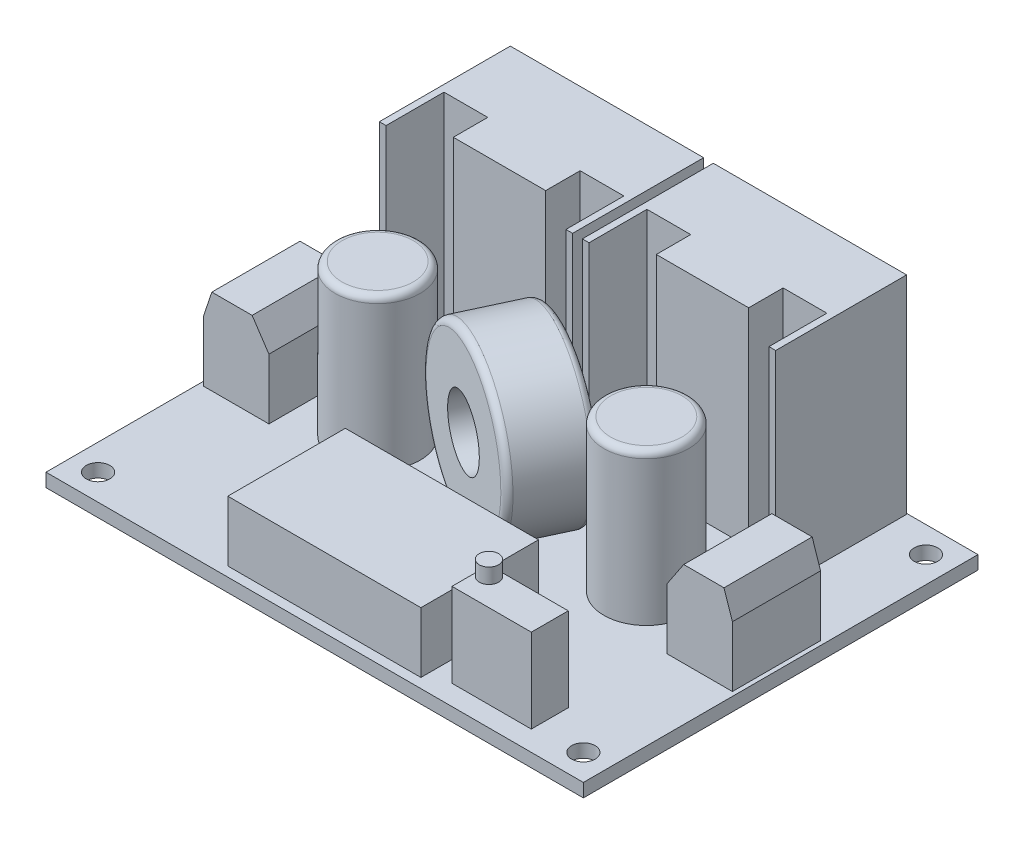
SolidWorks part; units mm, degrees
ref_plane "Front" through (0, 0, 0) normal (0, 0, 1) x (1, 0, 0)
ref_plane "Top" through (0, 0, 0) normal (0, 1, 0) x (1, 0, 0)
ref_plane "Right" through (0, 0, 0) normal (1, 0, 0) x (0, 0, -1)
sketch "Sketch1" plane through (0, 0, 0) normal (0, 1, 0) x (1, 0, 0)
  line L1 (-32, -23.5) -> (32, -23.5)
  line L2 (-32, -23.5) -> (-32, 23.5)
  line L3 (-32, 23.5) -> (32, 23.5)
  line L4 (32, -23.5) -> (32, 23.5)
  line L5 (-32, -23.5) -> (32, 23.5) construction
  line L6 (-32, 23.5) -> (32, -23.5) construction
  point P0 (0, 0)
  dimension "D1" = 47
  dimension "D2" = 64
extrude "Boss-Extrude1" add sketch "Sketch1" along normal blind 1.6
sketch "Sketch2" plane through (0, 1.6, 0) normal (0, 1, 0) x (1, 0, 0)
  line L0 (-27.6, 0) -> (27.6, 0) construction
  line L9 (-32, 23.5) -> (-32, -23.5) construction
  line L10 (-31.5, -5.25) -> (-23.7, -5.25)
  line L11 (-31.5, -5.25) -> (-31.5, 5.25)
  line L12 (-31.5, 5.25) -> (-23.7, 5.25)
  line L13 (-23.7, -5.25) -> (-23.7, 5.25)
  line L14 (-31.5, -5.25) -> (-23.7, 5.25) construction
  line L15 (-31.5, 5.25) -> (-23.7, -5.25) construction
  line L16 (23.7, -5.25) -> (31.5, -5.25)
  line L17 (23.7, -5.25) -> (23.7, 5.25)
  line L18 (23.7, 5.25) -> (31.5, 5.25)
  line L19 (31.5, -5.25) -> (31.5, 5.25)
  line L20 (23.7, -5.25) -> (31.5, 5.25) construction
  line L21 (23.7, 5.25) -> (31.5, -5.25) construction
  point P3 (0, 0)
  dimension "D1" = 7.8
  dimension "D2" = 10.5
  dimension "D3" = 0.5
extrude "Boss-Extrude2" add sketch "Sketch2" along normal blind 10.2
chamfer "Chamfer1" distance 3 distance2 2 2 edges at (23.7, 11.8, 0) (-23.7, 11.8, 0) first distance on face at (23.7, 6.7, 0) first distance on face at (-23.7, 6.7, 0)
chamfer "Chamfer2" distance 3 distance2 1 2 edges at (-31.5, 11.8, 0) (31.5, 11.8, 0) first distance on face at (-31.5, 6.7, 0) first distance on face at (31.5, 6.7, 0)
sketch "Sketch3" plane through (0, 1.6, 0) normal (0, 1, 0) x (1, 0, 0)
  line L0 (-16, 0) -> (16, 0) construction
  circle A0 centre (-16, 0) radius 5.05
  circle A1 centre (16, 0) radius 5.05
  point P8 (0, 0)
  dimension "D2" = 10.1
  dimension "D1" = 32
extrude "Boss-Extrude3" add sketch "Sketch3" along normal blind 18
ref_axis "Axis1" through (0, 0, 0) along (0, 1, 0)
ref_plane "Plane1" through (0, 0, 0) normal (-0.4226, 0, 0.9063) x (0, 1, 0)
sketch "Sketch4" plane through (0, 0, 0) normal (-0.4226, 0, 0.9063) x (0, 1, 0)
  circle A0 centre (11, 0) radius 10
  circle A1 centre (11, 0) radius 3.9
  dimension "D1" = 20
  dimension "D2" = 7.8
  dimension "D3" = 11
extrude "Boss-Extrude4" add sketch "Sketch4" along normal blind 4.35 and the other way blind 4.35
fillet "Fillet1" radius 0.8 4 edges at (1.8384, 21, -3.9424) (-1.8384, 21, 3.9424) (16, 19.6, 5.05) (-16, 19.6, 5.05)
sketch "Sketch5" plane through (0, 1.6, 0) normal (0, 1, 0) x (1, 0, 0)
  line L1 (-23.6, 23.4) -> (-0.575, 23.4)
  line L2 (-23.6, 23.4) -> (-23.6, 7.8)
  line L3 (-23.6, 7.8) -> (-22.8, 7.8)
  line L4 (23.6, 23.4) -> (23.6, 7.8)
  line L5 (-22.8, 7.8) -> (-22.8, 14.7)
  line L6 (-22.8, 14.7) -> (-17.5875, 14.7)
  line L7 (-17.5875, 14.7) -> (-17.5875, 10.6)
  line L8 (-17.5875, 10.6) -> (-6.5875, 10.6)
  line L9 (-6.5875, 10.6) -> (-6.5875, 14.7)
  line L10 (-6.5875, 14.7) -> (-1.375, 14.7)
  line L11 (-1.375, 14.7) -> (-1.375, 7.8)
  line L12 (-1.375, 7.8) -> (-0.575, 7.8)
  line L13 (-0.575, 7.8) -> (-0.575, 23.4)
  line L14 (0.575, 23.4) -> (0.575, 7.8)
  line L15 (0.575, 7.8) -> (1.375, 7.8)
  line L16 (1.375, 7.8) -> (1.375, 14.7)
  line L17 (1.375, 14.7) -> (6.5875, 14.7)
  line L18 (6.5875, 14.7) -> (6.5875, 10.6)
  line L19 (6.5875, 10.6) -> (17.5875, 10.6)
  line L20 (17.5875, 10.6) -> (17.5875, 14.7)
  line L21 (17.5875, 14.7) -> (22.8, 14.7)
  line L22 (22.8, 14.7) -> (22.8, 7.8)
  line L23 (-1.375, 7.8) -> (-0.575, 7.8)
  line L24 (22.8, 7.8) -> (23.6, 7.8)
  line L25 (0.575, 7.8) -> (1.375, 7.8)
  line L26 (0.575, 23.4) -> (23.6, 23.4)
  line L27 (-0.575, 15.6) -> (0.575, 15.6) construction
  line L28 (32, 23.5) -> (-32, 23.5) construction
  point P6 (0, 15.6)
  line M10 (32, 23.5) -> (-32, 23.5)
  dimension "D1" = 47.2
  dimension "D2" = 15.6
  dimension "D3" = 1.15
  dimension "D4" = 0.8
  dimension "D5" = 11
  dimension "D6" = 6.9
  dimension "D7" = 2.8
  dimension "D8" = 0.1
extrude "Boss-Extrude5" add sketch "Sketch5" along normal blind 24.7 contours L12 L13 L2 L3 L5 L6 L7 L8 L9 L10 L11 M10 | L22 L24 L4 L14 L15 L16 L17 L18 L19 L20 L21 M10 region at (-12.0875, 1.6, -17.5887) region at (12.0875, 1.6, -17.5887)
sketch "Sketch6" plane through (0, 1.6, 0) normal (0, 1, 0) x (1, 0, 0)
  line L0 (-32, 23.5) -> (-32, -23.5) construction
  line L1 (-11.5, -22.35) -> (11.5, -22.35)
  line L2 (-11.5, -22.35) -> (-11.5, -8.35)
  line L3 (-11.5, -8.35) -> (11.5, -8.35)
  line L4 (11.5, -22.35) -> (11.5, -8.35)
  line L5 (32, -23.5) -> (32, 23.5) construction
  line L6 (-32, -23.5) -> (32, -23.5) construction
  dimension "D1" = 20.5
  dimension "D2" = 20.5
  dimension "D3" = 14
  dimension "D4" = 1.15
extrude "Boss-Extrude6" add sketch "Sketch6" along normal blind 7.2
sketch "Sketch7" plane through (0, 1.6, 0) normal (0, 1, 0) x (1, 0, 0)
  line L0 (32, -23.5) -> (32, 23.5) construction
  line L1 (13.95, -21.1) -> (23.4, -21.1)
  line L2 (13.95, -21.1) -> (13.95, -16.7)
  line L3 (13.95, -16.7) -> (23.4, -16.7)
  line L4 (23.4, -21.1) -> (23.4, -16.7)
  line L5 (-32, -23.5) -> (32, -23.5) construction
  dimension "D1" = 4.4
  dimension "D2" = 9.45
  dimension "D3" = 8.6
  dimension "D4" = 2.4
extrude "Boss-Extrude7" add sketch "Sketch7" along normal blind 10
sketch "Sketch8" plane through (0, 11.6, 0) normal (0, 1, 0) x (1, 0, 0)
  line L0 (23.4, -16.7) -> (13.95, -16.7) construction
  line L1 (13.95, -16.7) -> (13.95, -21.1) construction
  circle A0 centre (15.15, -17.9) radius 1.15
  dimension "D1" = 2.3
  dimension "D2" = 1.2
  dimension "D3" = 1.2
extrude "Boss-Extrude8" add sketch "Sketch8" along normal blind 1.8
sketch "Sketch9" plane through (0, 1.6, 0) normal (0, 1, 0) x (1, 0, 0)
  line L1 (-28.9, -20.4) -> (28.9, -20.4) construction
  line L2 (-28.9, -20.4) -> (-28.9, 20.4) construction
  line L3 (-28.9, 20.4) -> (28.9, 20.4) construction
  line L4 (28.9, -20.4) -> (28.9, 20.4) construction
  line L5 (-28.9, -20.4) -> (28.9, 20.4) construction
  line L6 (-28.9, 20.4) -> (28.9, -20.4) construction
  circle A1 centre (-28.9, 20.4) radius 1.4
  circle A2 centre (28.9, 20.4) radius 1.4
  circle A3 centre (28.9, -20.4) radius 1.4
  circle A4 centre (-28.9, -20.4) radius 1.4
  point P0 (0, 0)
  dimension "D1" = 2.8
  dimension "D2" = 40.8
  dimension "D3" = 57.8
extrude "Cut-Extrude1" cut sketch "Sketch9" against normal through all
